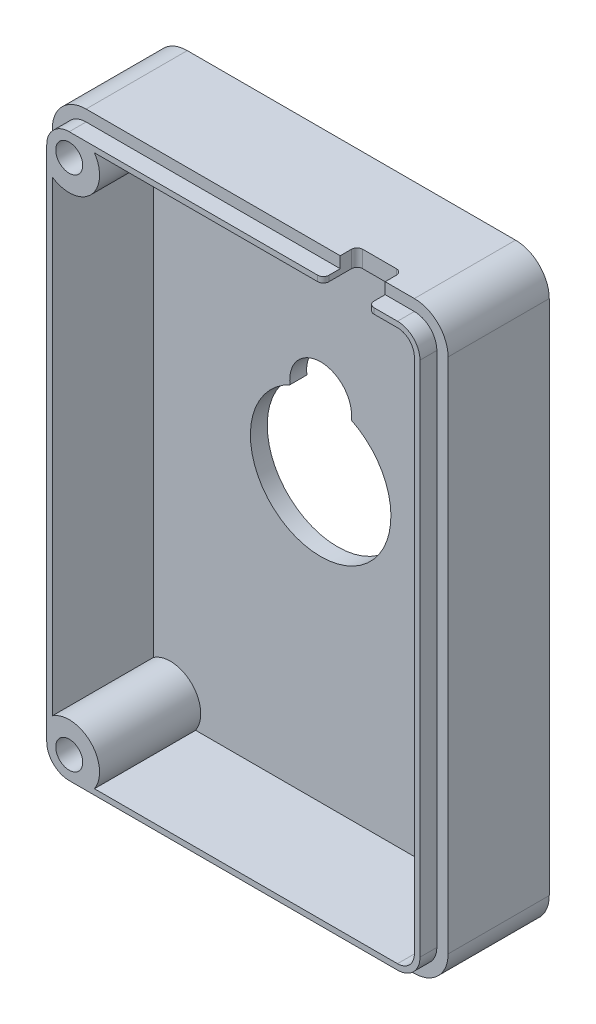
SolidWorks part; units mm, degrees
ref_plane "Front Plane" through (0, 0, 0) normal (0, 0, 1) x (1, 0, 0)
ref_plane "Top Plane" through (0, 0, 0) normal (0, 1, 0) x (1, 0, 0)
ref_plane "Right Plane" through (0, 0, 0) normal (1, 0, 0) x (0, 0, -1)
sketch "Sketch1" plane through (0, 0, 0) normal (0, 0, 1) x (1, 0, 0)
  line L0 (9.7396, 25.2956) -> (12.7396, 25.2956)
  line L7 (9.7396, 25.2956) -> (12.7396, 25.2956)
  line L8 (12.7396, 25.2956) -> (13.2396, 25.2956)
  line L9 (12.7396, 25.2956) -> (13.2396, 25.2956)
  line L10 (13.2396, 25.2956) -> (13.7396, 25.2956)
  line L11 (13.2396, 25.2956) -> (13.7396, 25.2956)
  line L12 (13.7396, 25.2956) -> (15.8346, 25.2956)
  line L13 (13.7396, 25.2956) -> (15.8346, 25.2956)
  line L14 (18.8346, 22.2956) -> (18.8346, -23.6932)
  line L15 (18.8346, 22.2956) -> (18.8346, -23.6932)
  line L16 (15.8346, -26.6932) -> (-13.3654, -26.6932)
  line L17 (15.8346, -26.6932) -> (-13.3654, -26.6932)
  line L18 (-16.3654, -23.6932) -> (-16.3654, 22.2956)
  line L19 (-16.3654, -23.6932) -> (-16.3654, 22.2956)
  line L20 (-13.3654, 25.2956) -> (8.7396, 25.2956)
  line L21 (-13.3654, 25.2956) -> (8.7396, 25.2956)
  line L22 (8.7396, 25.2956) -> (9.2396, 25.2956)
  line L23 (8.7396, 25.2956) -> (9.2396, 25.2956)
  line L24 (9.2396, 25.2956) -> (9.7396, 25.2956)
  line L25 (9.2396, 25.2956) -> (9.7396, 25.2956)
  arc A2 (-2.4465, 5.4786) -> (2.5188, 5.4457) centre (0, 0) ccw construction
  arc A3 (-2.7243, 5.625) -> (2.7243, 5.625) centre (0, 0) ccw
  arc A4 (2.5188, 5.4457) -> (-2.4465, 5.4786) centre (0.0397, 5.9976) ccw construction
  arc A5 (2.7243, 5.625) -> (-2.7243, 5.625) centre (0, 6) ccw
  circle A6 centre (0, 0) radius 6.25 construction
  circle A7 centre (0, 0) radius 6 construction
  arc A8 (18.8346, 22.2956) -> (15.8346, 25.2956) centre (15.8346, 22.2956) ccw
  arc A9 (18.8346, 22.2956) -> (15.8346, 25.2956) centre (15.8346, 22.2956) ccw
  arc A10 (15.8346, -26.6932) -> (18.8346, -23.6932) centre (15.8346, -23.6932) ccw
  arc A11 (15.8346, -26.6932) -> (18.8346, -23.6932) centre (15.8346, -23.6932) ccw
  arc A12 (-16.3654, -23.6932) -> (-13.3654, -26.6932) centre (-13.3654, -23.6932) ccw
  arc A13 (-16.3654, -23.6932) -> (-13.3654, -26.6932) centre (-13.3654, -23.6932) ccw
  arc A14 (-13.3654, 25.2956) -> (-16.3654, 22.2956) centre (-13.3654, 22.2956) ccw
  arc A15 (-13.3654, 25.2956) -> (-16.3654, 22.2956) centre (-13.3654, 22.2956) ccw
  dimension "D4" = 0.25
  dimension "D5" = 5.5
extrude "Exrude-Base" add sketch "Sketch1" along normal blind 1.5
sketch "Sketch2" plane through (0, 0, 1.5) normal (0, 0, 1) x (1, 0, 0)
  line L0 (18.8346, 22.2956) -> (18.8346, -23.6932)
  line L1 (18.8346, 22.2956) -> (18.8346, -23.6932)
  line L2 (15.8346, -26.6932) -> (-13.3654, -26.6932)
  line L3 (15.8346, -26.6932) -> (-13.3654, -26.6932)
  line L4 (-16.3654, -23.6932) -> (-16.3654, 22.2956)
  line L5 (-16.3654, -23.6932) -> (-16.3654, 22.2956)
  line L6 (-13.3654, 25.2956) -> (15.8346, 25.2956)
  line L7 (-13.3654, 25.2956) -> (15.8346, 25.2956)
  line L8 (17.3346, 22.2956) -> (17.3346, -23.6932)
  line L9 (15.8346, -25.1932) -> (-13.3654, -25.1932)
  line L10 (-14.8654, -23.6932) -> (-14.8654, 22.2956)
  line L11 (-13.3654, 23.7956) -> (15.8346, 23.7956)
  arc A0 (15.8346, -26.6932) -> (18.8346, -23.6932) centre (15.8346, -23.6932) ccw
  arc A1 (15.8346, -26.6932) -> (18.8346, -23.6932) centre (15.8346, -23.6932) ccw
  arc A2 (-16.3654, -23.6932) -> (-13.3654, -26.6932) centre (-13.3654, -23.6932) ccw
  arc A3 (-16.3654, -23.6932) -> (-13.3654, -26.6932) centre (-13.3654, -23.6932) ccw
  arc A4 (-13.3654, 25.2956) -> (-16.3654, 22.2956) centre (-13.3654, 22.2956) ccw
  arc A5 (-13.3654, 25.2956) -> (-16.3654, 22.2956) centre (-13.3654, 22.2956) ccw
  arc A6 (18.8346, 22.2956) -> (15.8346, 25.2956) centre (15.8346, 22.2956) ccw
  arc A7 (18.8346, 22.2956) -> (15.8346, 25.2956) centre (15.8346, 22.2956) ccw
  arc A8 (15.8346, -25.1932) -> (17.3346, -23.6932) centre (15.8346, -23.6932) ccw
  arc A9 (-14.8654, -23.6932) -> (-13.3654, -25.1932) centre (-13.3654, -23.6932) ccw
  arc A10 (-13.3654, 23.7956) -> (-14.8654, 22.2956) centre (-13.3654, 22.2956) ccw
  arc A11 (17.3346, 22.2956) -> (15.8346, 23.7956) centre (15.8346, 22.2956) ccw
  dimension "D1" = 1.5
extrude "Extrude-Sidewalls" add sketch "Sketch2" along normal blind 9
sketch "Sketch3" plane through (0, 0, 10.5) normal (0, 0, 1) x (1, 0, 0)
  line L0 (18.8346, 22.2956) -> (18.8346, -23.6932)
  line L1 (18.8346, 22.2956) -> (18.8346, -23.6932)
  line L2 (15.8346, -26.6932) -> (-13.3654, -26.6932)
  line L3 (15.8346, -26.6932) -> (-13.3654, -26.6932)
  line L4 (-16.3654, -23.6932) -> (-16.3654, 22.2956)
  line L5 (-16.3654, -23.6932) -> (-16.3654, 22.2956)
  line L6 (-13.3654, 25.2956) -> (15.8346, 25.2956)
  line L7 (-13.3654, 25.2956) -> (15.8346, 25.2956)
  line L8 (17.8346, 22.2956) -> (17.8346, -23.6932)
  line L9 (15.8346, -25.6932) -> (-13.3654, -25.6932)
  line L10 (-15.3654, -23.6932) -> (-15.3654, 22.2956)
  line L11 (-13.3654, 24.2956) -> (15.8346, 24.2956)
  arc A0 (15.8346, -26.6932) -> (18.8346, -23.6932) centre (15.8346, -23.6932) ccw
  arc A1 (15.8346, -26.6932) -> (18.8346, -23.6932) centre (15.8346, -23.6932) ccw
  arc A2 (-16.3654, -23.6932) -> (-13.3654, -26.6932) centre (-13.3654, -23.6932) ccw
  arc A3 (-16.3654, -23.6932) -> (-13.3654, -26.6932) centre (-13.3654, -23.6932) ccw
  arc A4 (-13.3654, 25.2956) -> (-16.3654, 22.2956) centre (-13.3654, 22.2956) ccw
  arc A5 (-13.3654, 25.2956) -> (-16.3654, 22.2956) centre (-13.3654, 22.2956) ccw
  arc A6 (18.8346, 22.2956) -> (15.8346, 25.2956) centre (15.8346, 22.2956) ccw
  arc A7 (18.8346, 22.2956) -> (15.8346, 25.2956) centre (15.8346, 22.2956) ccw
  arc A8 (15.8346, -25.6932) -> (17.8346, -23.6932) centre (15.8346, -23.6932) ccw
  arc A9 (-15.3654, -23.6932) -> (-13.3654, -25.6932) centre (-13.3654, -23.6932) ccw
  arc A10 (-13.3654, 24.2956) -> (-15.3654, 22.2956) centre (-13.3654, 22.2956) ccw
  arc A11 (17.8346, 22.2956) -> (15.8346, 24.2956) centre (15.8346, 22.2956) ccw
  dimension "D1" = 1
extrude "Partling-Line-Lip" cut sketch "Sketch3" against normal blind 1.5
sketch "Sketch4" plane through (0, 0, 1.5) normal (0, 0, 1) x (1, 0, 0)
  line L0 (14.6596, 23.2956) -> (14.6596, 2.5692) construction
  line L1 (15.3346, 23.2956) -> (13.9846, 23.2956) construction
  line L2 (12.1596, 23.7956) -> (13.6596, 23.7956)
  line L3 (15.8346, 23.7956) -> (-13.3654, 23.7956) construction
  line L4 (13.6596, 23.7956) -> (13.6596, 13.7956)
  line L5 (15.6596, 23.7956) -> (15.6596, 13.7956)
  line L6 (17.8115, 13.7956) -> (15.6596, 13.7956)
  line L7 (15.6596, 23.2956) -> (15.6596, 2.5692) construction
  line L8 (13.6596, 23.2956) -> (13.6596, 2.5692) construction
  line L9 (17.8115, 23.7956) -> (17.8115, 13.7956)
  line L10 (12.1596, 23.7956) -> (12.1596, 13.7956)
  line L11 (13.6596, 13.7956) -> (12.1596, 13.7956)
  line L12 (15.6596, 23.7956) -> (17.8115, 23.7956)
  point P6 (16.7355, 23.7956)
  dimension "D1" = 1
  dimension "D3" = 1.5
  dimension "D4" = 10
  dimension "D2" = 1
extrude "Boss-Extrude3" add sketch "Sketch4" along normal blind 1.5
fillet "Fillet2" radius 0.25 16 edges at (13.6596, 23.7956, 2.25) (12.9096, 13.7956, 1.5) (17.3346, 13.7956, 2.25) (15.6596, 23.7956, 2.25) (12.9096, 23.7956, 3) (13.6596, 18.7956, 3) (12.1596, 23.7956, 2.25) (12.1596, 18.7956, 3) (12.1596, 13.7956, 2.25) (12.1596, 18.7956, 1.5) (17.3346, 18.0456, 3) (16.4971, 13.7956, 3) (15.6596, 18.7956, 3) (16.8952, 23.3563, 3) (16.4971, 13.7956, 1.5) (12.9096, 13.7956, 3)
sketch "Sketch5" plane through (0, 25.2956, 0) normal (0, 1, 0) x (1, 0, 0)
  line L0 (9.2396, -10.5) -> (9.2396, -8)
  line L2 (13.2396, -10.5) -> (13.2396, -8)
  line L4 (9.7396, -7.5) -> (12.7396, -7.5)
  line L5 (9.2396, -10.5) -> (13.2396, -10.5)
  line L7 (15.8346, -10.5) -> (-13.3654, -10.5) construction
  arc A0 (13.2396, -8) -> (12.7396, -7.5) centre (12.7396, -8) ccw
  arc A1 (9.7396, -7.5) -> (9.2396, -8) centre (9.7396, -8) ccw
  point P9 (9.2396, -7.5)
  dimension "D3" = 0.5
  dimension "D1" = 4
  dimension "D2" = 3
extrude "Cut-Extrude2" cut sketch "Sketch5" against normal blind 1.5
fillet "Fillet3" radius 0.5 2 edges at (13.2396, 24.0456, 10.5) (9.2396, 24.0456, 10.5)
sketch "Screw-Holes" plane through (0, 0, 1.5) normal (0, 0, 1) x (1, 0, 0)
  circle A0 centre (-13.3654, 22.2956) radius 1.2
  circle A1 centre (-13.3654, -23.6932) radius 1.2
  dimension "D1" = 2.4
sketch "Sketch7" plane through (0, 0, 1.5) normal (0, 0, 1) x (1, 0, 0)
  line L0 (-13.3654, -25.1932) -> (15.8346, -25.1932) construction
  line L1 (11.9096, 23.7956) -> (-13.3654, 23.7956) construction
  line L2 (-14.8654, 22.2956) -> (-14.8654, -23.6932) construction
  line L3 (-13.3654, -25.1932) -> (-11.1204, -25.1932)
  line L4 (-11.1204, 23.7956) -> (-13.3654, 23.7956)
  line L5 (-14.8654, 22.2956) -> (-14.8654, 20.0506)
  line L6 (-14.8654, -21.4482) -> (-14.8654, -23.6932)
  arc A0 (-14.8654, 20.0506) -> (-11.1204, 23.7956) centre (-13.3654, 22.2956) ccw
  arc A1 (-11.1204, -25.1932) -> (-14.8654, -21.4482) centre (-13.3654, -23.6932) ccw
  arc A2 (-13.3654, 23.7956) -> (-14.8654, 22.2956) centre (-13.3654, 22.2956) ccw
  arc A3 (-14.8654, -23.6932) -> (-13.3654, -25.1932) centre (-13.3654, -23.6932) ccw
  dimension "D1" = 5.4
extrude "ScrewBoss" add sketch "Sketch7" along normal up to vertex (9 mm away)
extrude "ScrewHole" cut sketch "Screw-Holes" against normal through all both and the other way through all
sketch "Sketch8" plane through (0, 0, 0) normal (0, 0, -1) x (-1, 0, 0)
  circle A0 centre (13.3654, 22.2956) radius 2.2
  circle A1 centre (13.3654, -23.6932) radius 2.2
  dimension "D1" = 4.4
extrude "Cut-Extrude4" cut sketch "Sketch8" against normal blind 2.6
equation "\"D1@Sketch7\"=2.4+3"
